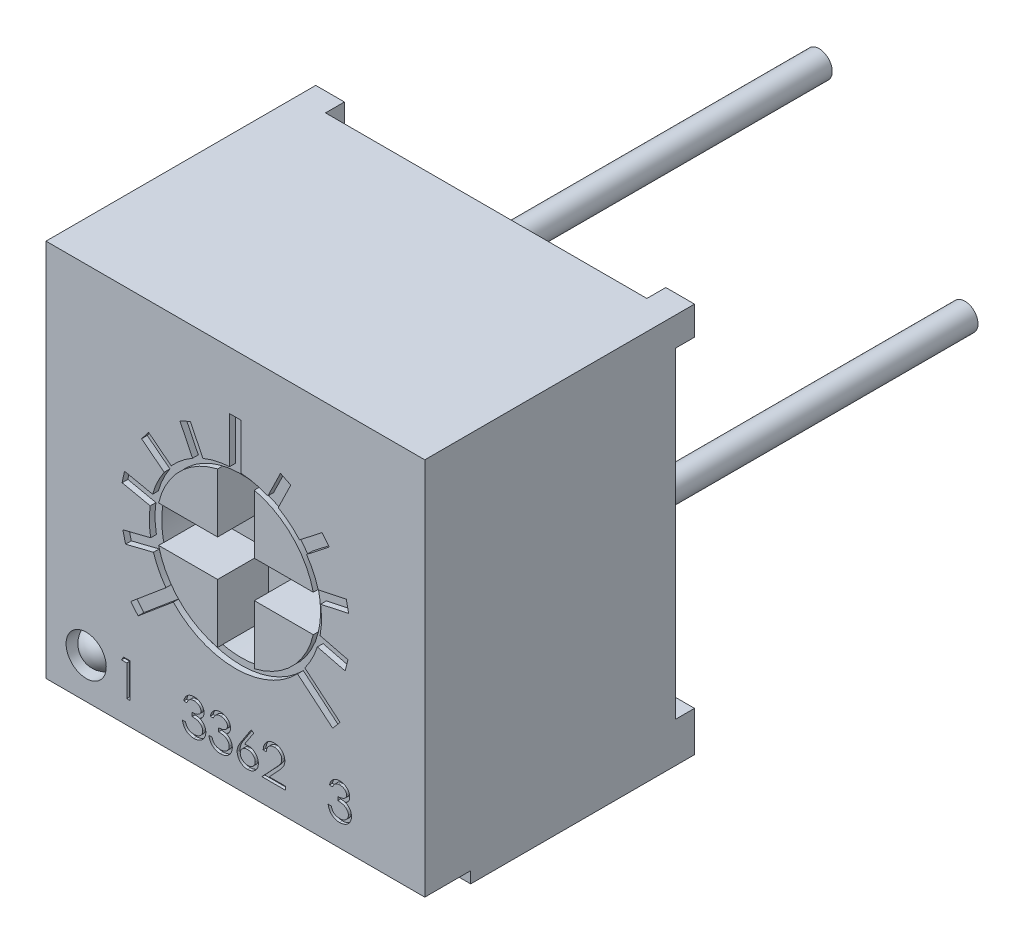
SolidWorks part; units mm, degrees
ref_plane "Front Plane" through (0, 0, 0) normal (0, 0, 1) x (1, 0, 0)
ref_plane "Top Plane" through (0, 0, 0) normal (0, 1, 0) x (1, 0, 0)
ref_plane "Right Plane" through (0, 0, 0) normal (1, 0, 0) x (0, 0, -1)
sketch "Эскиз1" plane through (0, 0, 0) normal (0, 0, 1) x (1, 0, 0)
  line L1 (-3.3, 3.3) -> (3.3, 3.3)
  line L2 (-3.3, 3.3) -> (-3.3, -3.3)
  line L3 (-3.3, -3.3) -> (3.3, -3.3)
  line L4 (3.3, 3.3) -> (3.3, -3.3)
  line L5 (-3.3, 3.3) -> (3.3, -3.3) construction
  line L6 (-3.3, -3.3) -> (3.3, 3.3) construction
  point P0 (0, 0)
  dimension "D1" = 6.6
  dimension "D2" = 6.6
extrude "Бобышка-Вытянуть1" add sketch "Эскиз1" along normal blind 4.7
sketch "Эскиз2" plane through (0, 0, 4.7) normal (0, 0, 1) x (1, 0, 0)
  circle A0 centre (0, 0) radius 1.385
  dimension "D1" = 2.77
extrude "Вырез-Вытянуть1" cut sketch "Эскиз2" against normal blind 0.9
sketch "Эскиз3" plane through (0, 0, 3.8) normal (0, 0, 1) x (1, 0, 0)
  line L0 (-0.32, 1.3475) -> (-0.32, 0.32)
  line L1 (0.32, 1.3475) -> (0.32, 0.32)
  line L2 (-1.3475, 0.32) -> (-0.32, 0.32)
  line L3 (-1.3475, -0.32) -> (-0.32, -0.32)
  line L4 (0.32, 0.32) -> (1.3475, 0.32)
  line L5 (0.32, -0.32) -> (1.3475, -0.32)
  line L6 (0.32, -0.32) -> (0.32, -1.3475)
  line L7 (-0.32, -0.32) -> (-0.32, -1.3475)
  arc A0 (-0.32, 1.3475) -> (-1.3475, 0.32) centre (0, 0) ccw
  arc A2 (0.32, -1.3475) -> (1.3475, -0.32) centre (0, 0) ccw
  arc A3 (1.3475, 0.32) -> (0.32, 1.3475) centre (0, 0) ccw
  arc A4 (-1.3475, -0.32) -> (-0.32, -1.3475) centre (0, 0) ccw
  dimension "D5" = 1.385
  dimension "D1" = 0.64
  dimension "D2" = 0.32
  dimension "D3" = 0.64
  dimension "D4" = 0.32
extrude "Бобышка-Вытянуть2" add sketch "Эскиз3" along normal blind 0.89 separate body
sketch "Эскиз4" plane through (0, 0, 4.7) normal (0, 0, 1) x (1, 0, 0)
  line L0 (-0.1, 2.2967) -> (-0.1, 1.4967)
  line L1 (-0.1, 2.2967) -> (0.1, 2.2967)
  line L2 (-1.9615, -0.386) -> (-1.4764, -0.265)
  line L3 (0.1, 2.2967) -> (0.1, 1.4967)
  line L4 (-0.1, 2.2967) -> (0.1, 1.4967) construction
  line L5 (-0.1, 1.4967) -> (0.1, 2.2967) construction
  line L6 (-1.8236, -1.3997) -> (-1.2108, -0.8854)
  line L7 (-1.8236, -1.3997) -> (-1.6951, -1.5529)
  line L8 (-1.6948, -0.4226) -> (0, 0) construction
  line L9 (-1.6951, -1.5529) -> (-1.0822, -1.0386)
  line L10 (-1.8236, -1.3997) -> (-1.0822, -1.0386) construction
  line L11 (-1.2108, -0.8854) -> (-1.6951, -1.5529) construction
  line L12 (1.6951, -1.5529) -> (1.0822, -1.0386)
  line L13 (1.6951, -1.5529) -> (1.8236, -1.3997)
  line L14 (0, 0) -> (-0.7657, 1.5699) construction
  line L15 (1.8236, -1.3997) -> (1.2108, -0.8854)
  line L16 (1.6951, -1.5529) -> (1.2108, -0.8854) construction
  line L17 (1.0822, -1.0386) -> (1.8236, -1.3997) construction
  line L18 (-1.4529, -1.2192) -> (0, 0) construction
  line L19 (1.4529, -1.2192) -> (0, 0) construction
  line L20 (0, 1.8967) -> (0, 0) construction
  line L21 (-1.9615, -0.386) -> (-1.9132, -0.5801)
  line L23 (-1.9132, -0.5801) -> (-1.428, -0.4591)
  line L24 (-1.9615, -0.386) -> (-1.428, -0.4591) construction
  line L25 (-1.7085, 0.3632) -> (0, 0) construction
  line L26 (0, 0) -> (-1.3764, 1.0754) construction
  line L27 (0, 0) -> (0.7657, 1.5699) construction
  line L28 (0, 0) -> (1.3764, 1.0754) construction
  line L29 (0, 0) -> (1.7085, 0.3632) construction
  line L30 (0, 0) -> (1.6948, -0.4226) construction
  line L31 (-1.4764, -0.265) -> (-1.9132, -0.5801) construction
  line L32 (-1.9322, 0.5129) -> (-1.4432, 0.409)
  line L33 (-1.9322, 0.5129) -> (-1.9738, 0.3173)
  line L35 (-1.9738, 0.3173) -> (-1.4847, 0.2134)
  line L36 (-1.9322, 0.5129) -> (-1.4847, 0.2134) construction
  line L37 (-1.4432, 0.409) -> (-1.9738, 0.3173) construction
  line L38 (-1.5118, 1.3081) -> (-1.1178, 1.0002)
  line L39 (-1.5118, 1.3081) -> (-1.635, 1.1505)
  line L41 (-1.635, 1.1505) -> (-1.241, 0.8426)
  line L42 (-1.5118, 1.3081) -> (-1.241, 0.8426) construction
  line L43 (-1.1178, 1.0002) -> (-1.635, 1.1505) construction
  line L44 (-0.7854, 1.8384) -> (-0.5662, 1.389)
  line L45 (-0.7854, 1.8384) -> (-0.9652, 1.7508)
  line L47 (-0.9652, 1.7508) -> (-0.746, 1.3014)
  line L48 (-0.7854, 1.8384) -> (-0.746, 1.3014) construction
  line L49 (-0.5662, 1.389) -> (-0.9652, 1.7508) construction
  line L50 (0.7854, 1.8384) -> (0.5662, 1.389)
  line L51 (0.7854, 1.8384) -> (0.9652, 1.7508)
  line L53 (0.9652, 1.7508) -> (0.746, 1.3014)
  line L54 (0.7854, 1.8384) -> (0.746, 1.3014) construction
  line L55 (0.5662, 1.389) -> (0.9652, 1.7508) construction
  line L56 (1.5118, 1.3081) -> (1.1178, 1.0002)
  line L57 (1.5118, 1.3081) -> (1.635, 1.1505)
  line L59 (1.635, 1.1505) -> (1.241, 0.8426)
  line L60 (1.5118, 1.3081) -> (1.241, 0.8426) construction
  line L61 (1.1178, 1.0002) -> (1.635, 1.1505) construction
  line L62 (1.9322, 0.5129) -> (1.4432, 0.409)
  line L63 (1.9322, 0.5129) -> (1.9738, 0.3173)
  line L65 (1.9738, 0.3173) -> (1.4847, 0.2134)
  line L66 (1.9322, 0.5129) -> (1.4847, 0.2134) construction
  line L67 (1.4432, 0.409) -> (1.9738, 0.3173) construction
  line L68 (1.9132, -0.5801) -> (1.428, -0.4591)
  line L69 (1.9132, -0.5801) -> (1.9615, -0.386)
  line L71 (1.9615, -0.386) -> (1.4764, -0.265)
  line L72 (1.9132, -0.5801) -> (1.4764, -0.265) construction
  line L73 (1.428, -0.4591) -> (1.9615, -0.386) construction
  circle A0 centre (0, 0) radius 1.385
  arc A1 (-0.1, 1.4967) -> (-0.5662, 1.389) centre (0, 0) ccw
  circle A2 centre (0, 0) radius 1.385 construction
  arc A3 (1.4764, -0.265) -> (1.4847, 0.2134) centre (0, 0) ccw
  arc A4 (-1.0822, -1.0386) -> (1.0822, -1.0386) centre (0, 0) ccw
  arc A5 (1.2108, -0.8854) -> (1.428, -0.4591) centre (0, 0) ccw
  arc A6 (1.4432, 0.409) -> (1.241, 0.8426) centre (0, 0) ccw
  arc A7 (1.1178, 1.0002) -> (0.746, 1.3014) centre (0, 0) ccw
  arc A8 (0.5662, 1.389) -> (0.1, 1.4967) centre (0, 0) ccw
  arc A9 (-0.746, 1.3014) -> (-1.1178, 1.0002) centre (0, 0) ccw
  arc A10 (-1.241, 0.8426) -> (-1.4432, 0.409) centre (0, 0) ccw
  arc A11 (-1.4847, 0.2134) -> (-1.4764, -0.265) centre (0, 0) ccw
  arc A12 (-1.428, -0.4591) -> (-1.2108, -0.8854) centre (0, 0) ccw
  point P7 (0, 1.8967)
  point P8 (-1.4529, -1.2192)
  point P9 (1.4529, -1.2192)
  dimension "D1" = 3
  dimension "D2" = 0.2
  dimension "D3" = 0.8
  dimension "D4" = 0.8
  dimension "D5" = 0.2
  dimension "D6" = 0.2
  dimension "D7" = 0.8
  dimension "D8" = 130
  dimension "D9" = 130
  dimension "D10" = 26
  dimension "D11" = 26
  dimension "D12" = 26
  dimension "D13" = 26
  dimension "D14" = 26
  dimension "D15" = 26
  dimension "D16" = 26
  dimension "D17" = 26
  dimension "D18" = 0.5
  dimension "D19" = 0.2
  dimension "D20" = 0.5
  dimension "D21" = 0.2
  dimension "D22" = 0.5
  dimension "D23" = 0.2
  dimension "D24" = 0.2
  dimension "D25" = 0.5
  dimension "D26" = 0.5
  dimension "D27" = 0.2
  dimension "D28" = 0.2
  dimension "D29" = 0.2
  dimension "D30" = 0.2
  dimension "D31" = 0.5
  dimension "D32" = 0.5
  dimension "D33" = 0.5
extrude "Вырез-Вытянуть2" cut sketch "Эскиз4" against normal blind 0.1
sketch "Эскиз6" plane through (0, 0, 4.7) normal (0, 0, 1) x (1, 0, 0)
  line L0 (-3.3, 3.3) -> (-3.3, -3.3) construction
  line L1 (-3.3, -3.3) -> (3.3, -3.3) construction
  circle A0 centre (-2.6, -2.6) radius 0.35
  dimension "D1" = 0.7
  dimension "D2" = 0.7
  dimension "D3" = 0.7
extrude "Вырез-Вытянуть3" cut sketch "Эскиз6" against normal blind 0.35
dome "Купол1" faces to dome 1 distance 0.35 reverse direction no elliptical dome no face at (-2.25, -2.6, 4.35) parameters "D1"=0.35
sketch "Эскиз13" plane through (0, -3.3, 0) normal (0, -1, 0) x (1, 0, 0)
  line L1 (-3.3, 4.7) -> (3.3, 4.7) construction
  line L2 (-3.3, 0) -> (3.3, 0) construction
  line L3 (-3.3, 3.9) -> (-2.77, 3.9)
  line L4 (-3.3, 3.9) -> (-3.3, 0)
  line L6 (-3.3, 0) -> (-2.77, 0)
  line L7 (-2.77, 3.9) -> (-2.77, 0)
  line L9 (-2.31, 3.9) -> (-0.23, 3.9)
  line L10 (-2.31, 3.9) -> (-2.31, 0)
  line L11 (-2.31, 0) -> (-0.23, 0)
  line L12 (-0.23, 3.9) -> (-0.23, 0)
  line L13 (0.23, 3.9) -> (2.31, 3.9)
  line L14 (-3.3, 3.9) -> (3.3, 3.9) construction
  line L15 (0.23, 3.9) -> (0.23, 0)
  line L16 (0.23, 0) -> (2.31, 0)
  line L17 (2.31, 3.9) -> (2.31, 0)
  line L18 (2.77, 3.9) -> (3.3, 3.9)
  line L19 (2.77, 3.9) -> (2.77, 0)
  line L20 (2.77, 0) -> (3.3, 0)
  line L21 (3.3, 3.9) -> (3.3, 0)
  dimension "D1" = 0.8
  dimension "D2" = 0.46
  dimension "D3" = 0.46
  dimension "D4" = 0.46
  dimension "D5" = 0.23
  dimension "D6" = 2.31
  dimension "D7" = 2.31
extrude "Бобышка-Вытянуть4" add sketch "Эскиз13" along normal blind 0.2
sketch "Эскиз14" plane through (0, -3.5, 0) normal (0, -1, 0) x (-1, 0, 0)
  line L0 (2.31, 0) -> (0.23, 0) construction
  line L1 (2.31, -3.9) -> (1.27, -3.9)
  line L2 (2.31, -3.9) -> (2.31, 0)
  line L3 (2.31, 0) -> (1.27, 0)
  line L4 (1.27, -3.9) -> (1.27, 0)
  line L5 (-0.23, 0) -> (-2.31, 0) construction
  line L6 (-2.31, -3.9) -> (-1.27, -3.9)
  line L7 (-2.31, -3.9) -> (-2.31, 0)
  line L8 (-2.31, 0) -> (-1.27, 0)
  line L9 (-1.27, -3.9) -> (-1.27, 0)
extrude "Бобышка-Вытянуть5" add sketch "Эскиз14" along normal blind 0.254
sketch "Эскиз8" plane through (0, 3.3, 0) normal (0, 1, 0) x (1, 0, 0)
  line L0 (3.3, 0) -> (-3.3, 0) construction
  line L1 (-2.8, 0) -> (2.8, 0)
  line L2 (-2.8, 0) -> (-2.8, -0.33)
  line L3 (-2.8, -0.33) -> (2.8, -0.33)
  line L4 (2.8, 0) -> (2.8, -0.33)
  line L5 (-3.3, -4.7) -> (-3.3, 0) construction
  line L6 (3.3, -4.7) -> (3.3, 0) construction
  dimension "D1" = 0.5
  dimension "D2" = 0.5
  dimension "D3" = 0.33
extrude "Вырез-Вытянуть4" cut sketch "Эскиз8" against normal through all
sketch "Эскиз9" plane through (3.3, 0, 0) normal (1, 0, 0) x (0, 0, -1)
  line L0 (0, -3.5) -> (0, 3.3) construction
  line L1 (0, 2.8) -> (-0.33, 2.8)
  line L2 (0, 2.8) -> (0, -2.8)
  line L3 (0, -2.8) -> (-0.33, -2.8)
  line L4 (-0.33, 2.8) -> (-0.33, -2.8)
  line L5 (-4.7, -3.3) -> (-3.9, -3.3) construction
  line L6 (-4.7, 3.3) -> (0, 3.3) construction
  dimension "D1" = 0.5
  dimension "D2" = 0.5
  dimension "D3" = 0.33
extrude "Вырез-Вытянуть5" cut sketch "Эскиз9" against normal through all
sketch "Эскиз10" plane through (0, 0, 0.33) normal (0, 0, -1) x (-1, 0, 0)
  circle A0 centre (-2.54, 0) radius 0.23
  circle A1 centre (2.54, 0) radius 0.23
  circle A2 centre (0, 2.54) radius 0.23
  dimension "D1" = 0.46
  dimension "D2" = 2.54
  dimension "D3" = 2.54
  dimension "D4" = 2.54
extrude "Бобышка-Вытянуть3" add sketch "Эскиз10" along normal blind 5.8 separate body
sketch "Эскиз11" plane through (0, 0, 4.7) normal (0, 0, 1) x (1, 0, 0)
  line L0 (-3.3, -3.3) -> (3.3, -3.3) construction
  line L2 (-3.3, 3.3) -> (-3.3, -3.3) construction
  text T0 "1   3362   3" font "Century Gothic" height 0.6
  point P5 (-2.1, -2.9)
  dimension "D1" = 0.4
  dimension "D2" = 1.2
extrude "Вырез-Вытянуть6" cut sketch "Эскиз11" against normal blind 0.05
